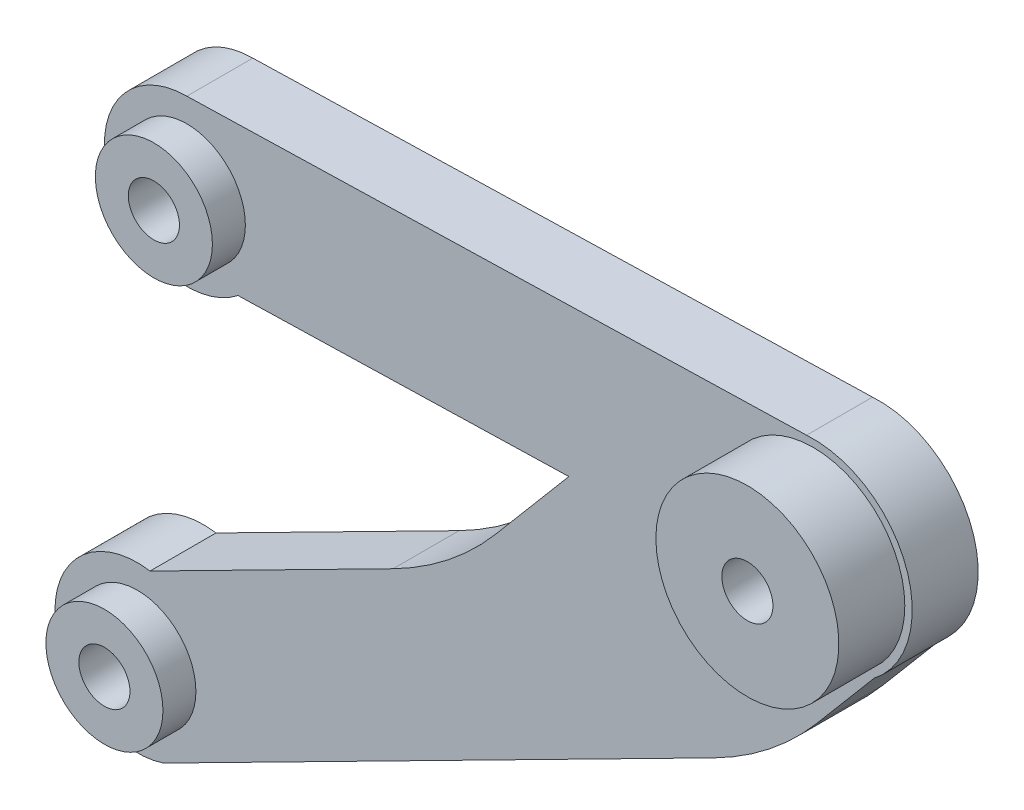
SolidWorks part; units mm, degrees
ref_plane "Front Plane" through (0, 0, 0) normal (0, 0, 1) x (1, 0, 0)
ref_plane "Top Plane" through (0, 0, 0) normal (0, 1, 0) x (1, 0, 0)
ref_plane "Right Plane" through (0, 0, 0) normal (1, 0, 0) x (0, 0, -1)
sketch "Sketch2" plane through (0, 0, 0) normal (0, 0, 1) x (1, 0, 0)
  line L0 (0, 0) -> (0, 26) construction
  line L1 (41, 26) -> (0, 26) construction
  line L2 (0, 0) -> (0, 26) construction
  line L3 (0, 26) -> (3, 26) construction
  line L4 (1.5758, -4.7452) -> (38.5983, 14.0699)
  line L5 (38.5983, 14.0699) -> (44.6837, 21.264)
  line L6 (3, 31) -> (40.5909, 31.986)
  line L10 (26.171, 22.6047) -> (19.1158, 14.2643)
  line L11 (19.1158, 14.2643) -> (0.7692, 4.9405)
  line L12 (6.1016, 22.0783) -> (26.171, 22.6047)
  circle A0 centre (0, 0) radius 1.55
  circle A1 centre (41, 26) radius 1.55
  circle A2 centre (3, 26) radius 1.55
  arc A3 (0.7692, 4.9405) -> (1.5758, -4.7452) centre (0, 0) ccw
  arc A4 (44.6837, 21.264) -> (40.5909, 31.986) centre (41, 26) ccw
  arc A5 (3, 31) -> (6.1016, 22.0783) centre (3, 26) ccw
  dimension "D1" = 3.1
  dimension "D2" = 3.1
  dimension "D3" = 3.1
  dimension "D8" = 10
  dimension "D9" = 12
  dimension "D10" = 10
  dimension "D5" = 41
  dimension "D6" = 26
  dimension "D7" = 3
  dimension "D11" = 9
  dimension "D12" = 9
  dimension "D13" = 15
extrude "Boss-Extrude1" add sketch "Sketch2" along normal blind 2 and the other way blind 2 contours L6 A5 A3 L4 L5 A4 A0 A1 A2 region at (-4.3468, -0.3619, 0)
fillet "Fillet1" radius 20 2 edges at (38.5983, 14.0699, 0) (19.1158, 14.2643, 0)
sketch "Sketch3" plane through (0, 0, 2) normal (0, 0, 1) x (1, 0, 0)
  line L0 (44.6837, 21.264) -> (26.4129, -0.3351)
  line L1 (41.2064, 17.1532) -> (44.6837, 21.264) construction
  line L2 (26.4129, -0.3351) -> (34.7488, -7.3866)
  line L3 (34.7488, -7.3866) -> (43.0769, 2.4586)
  line L4 (44.6837, 21.264) -> (53.0197, 14.2125)
  line L5 (53.0197, 14.2125) -> (44.6915, 4.3673)
  line L6 (43.0769, 2.4586) -> (30.2338, -2.2575)
  line L7 (30.2338, -2.2575) -> (47.213, 17.8147)
  line L8 (47.213, 17.8147) -> (44.6915, 4.3673)
  line L9 (30.2338, -2.2575) -> (29.588, -3.021) construction
  line L10 (47.213, 17.8147) -> (47.8588, 18.5781) construction
  dimension "D1" = 1
  dimension "D2" = 2.5
extrude "Boss-Extrude2" [suppressed] add sketch "Sketch3" against normal up to surface (10 mm away)
fillet "Fillet2" [suppressed] radius 1
sketch "Sketch4" plane through (0, 0, 2) normal (0, 0, 1) x (1, 0, 0)
  line L7 (41.2064, 17.1532) -> (44.6837, 21.264) construction
  line L8 (0, 0) -> (50000, 0) construction
  line L17 (44.6837, 21.264) -> (47.1283, 17.3372)
  line L18 (41.0014, 32) -> (48.527, 32)
  line L19 (48.527, 32) -> (54.0756, 21.2914)
  line L20 (52.0144, 16.8475) -> (52.5897, 16.0258)
  line L21 (52.461, 17.1603) -> (53.0363, 16.3386)
  line L22 (50.5241, 19.4512) -> (-28628.2978, 40977.0534) construction
  arc A0 (41.0014, 32) -> (44.6837, 21.264) centre (41, 26) cw
  arc A1 (44.6837, 21.264) -> (40.5909, 31.986) centre (41, 26) ccw construction
  arc A3 (52.461, 17.1603) -> (52.0144, 16.8475) centre (50.5241, 19.4512) ccw
  arc A4 (47.1283, 17.3372) -> (52.5897, 16.0258) centre (50.5241, 19.4512) ccw
  arc A5 (53.0363, 16.3386) -> (54.0756, 21.2914) centre (50.5241, 19.4512) ccw
  dimension "D1" = 6
  dimension "D2" = 8
  dimension "D3" = 55
extrude "Boss-Extrude3" [suppressed] add sketch "Sketch4" against normal up to surface (4 mm away)
fillet "Fillet3" [suppressed] radius 6
sketch "Sketch7" plane through (0, 0, 2) normal (0, 0, -1) x (-1, 0, 0)
  circle A0 centre (-41, 26) radius 1.55
  circle A1 centre (-41, 26) radius 5.55
  dimension "D1" = 4
extrude "Boss-Extrude4" add sketch "Sketch7" against normal blind 4
sketch "Sketch8" plane through (0, 0, 2) normal (0, 0, 1) x (1, 0, 0)
  circle A0 centre (3, 26) radius 1.55
  circle A1 centre (3, 26) radius 3.55
  circle A2 centre (0, 0) radius 1.55
  circle A3 centre (0, 0) radius 3.55
  dimension "D1" = 2
  dimension "D2" = 2
extrude "Boss-Extrude5" add sketch "Sketch8" along normal blind 2
